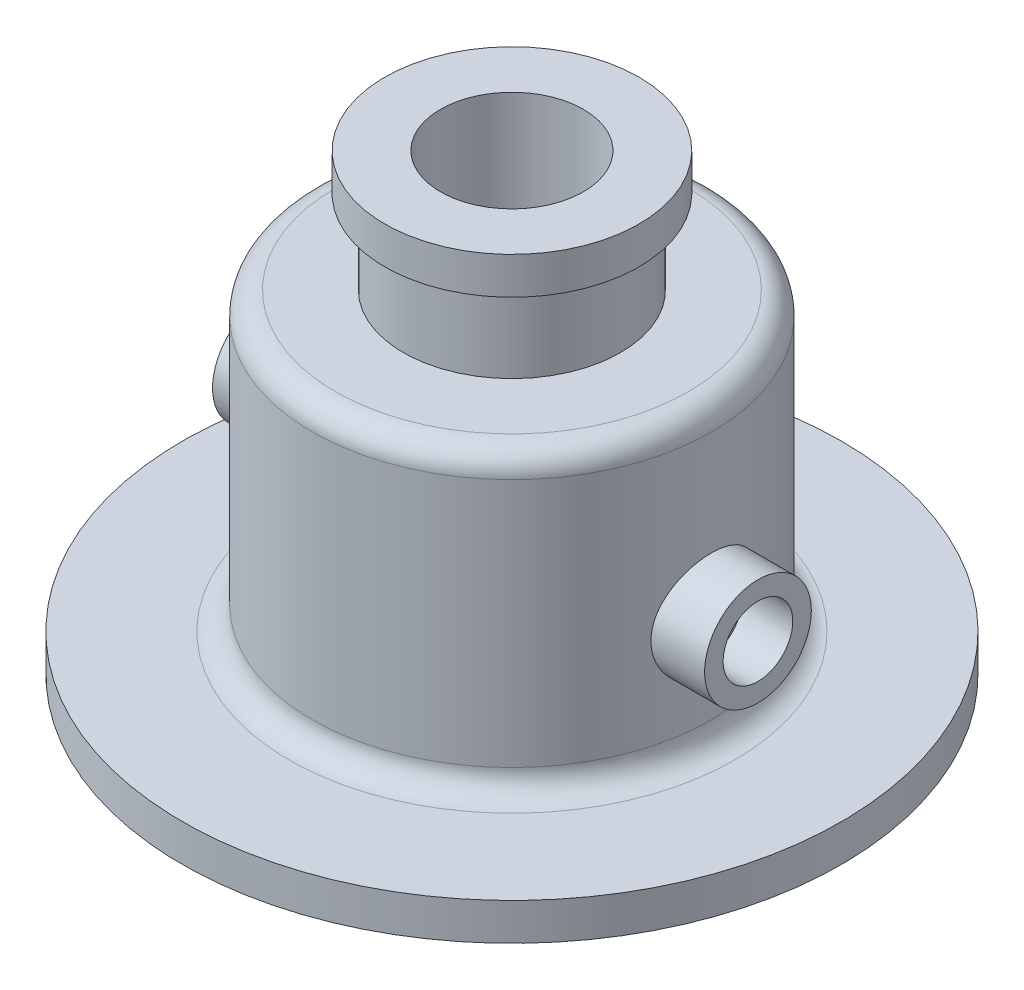
SolidWorks part; units mm, degrees
ref_plane "Front Plane" through (0, 0, 0) normal (0, 0, 1) x (1, 0, 0)
ref_plane "Top Plane" through (0, 0, 0) normal (0, 1, 0) x (1, 0, 0)
ref_plane "Right Plane" through (0, 0, 0) normal (1, 0, 0) x (0, 0, -1)
sketch "Sketch1" plane through (0, 0, 0) normal (0, 0, 1) x (1, 0, 0)
  line L0 (0, 0) -> (0, 43534.5217) construction
  line L1 (0, 0) -> (-43534.5217, 0) construction
  line L2 (15.4, 52.7) -> (15.4, 16.7)
  line L3 (15.4, 16.7) -> (23.4, 16.7)
  line L4 (23.4, 16.7) -> (23.4, 18.7)
  line L5 (23.4, 18.7) -> (30, 18.7)
  line L6 (35, 13.7) -> (35, -27)
  line L7 (30, -32) -> (25, -32)
  line L8 (25, -32) -> (25, -50)
  line L9 (25, -50) -> (32, -50)
  line L10 (32, -50) -> (32, -47)
  line L11 (34, -45) -> (71, -45)
  line L12 (71, -45) -> (71, -37)
  line L13 (71, -37) -> (48, -37)
  line L14 (43, -32) -> (43, 21.7)
  line L15 (38, 26.7) -> (23.4, 26.7)
  line L16 (23.4, 26.7) -> (23.4, 44.7)
  line L17 (23.4, 44.7) -> (27.4, 44.7)
  line L18 (27.4, 44.7) -> (27.4, 52.7)
  line L19 (27.4, 52.7) -> (15.4, 52.7)
  arc A0 (32, -47) -> (34, -45) centre (34, -47) cw
  arc A1 (48, -37) -> (43, -32) centre (48, -32) cw
  arc A2 (35, -27) -> (30, -32) centre (30, -27) cw
  arc A3 (30, 18.7) -> (35, 13.7) centre (30, 13.7) cw
  arc A4 (43, 21.7) -> (38, 26.7) centre (38, 21.7) ccw
  point P18 (23.4, 35.7)
  point P24 (28.5, -50)
  dimension "D19" = 2
  dimension "D20" = 5
  dimension "D1" = 7
  dimension "D2" = 8
  dimension "D3" = 2
  dimension "D4" = 8
  dimension "D5" = 8
  dimension "D6" = 8
  dimension "D7" = 48.7
  dimension "D8" = 15.4
  dimension "D9" = 8
  dimension "D10" = 35
  dimension "D11" = 5
  dimension "D12" = 25
  dimension "D13" = 71
  dimension "D14" = 34
  dimension "D15" = 4
  dimension "D16" = 18
  dimension "D17" = 5
  dimension "D18" = 50
revolve "Revolve1" add sketch "Sketch1" angle 360 about L0
chamfer "Chamfer1" distance 2 angle 45 1 edges at (0, 16.7, -15.4)
ref_plane "Plane1" through (53, 0, 0) normal (1, 0, 0) x (0, 0, -1)
ref_axis "Axis1" through (0, 52.7, 0) along (0, -1, 0)
sketch "Sketch2" plane through (53, 0, 0) normal (1, 0, 0) x (0, 0, -1)
  line L0 (-34, -45) -> (34, -45) construction
  circle A0 centre (0, -12.35) radius 7.5
  circle A1 centre (0, -12.35) radius 11.5
  dimension "D1" = 23
  dimension "D2" = 15
  dimension "D3" = 32.65
extrude "Boss-Extrude1" add sketch "Sketch2" against normal blind 106
sketch "Sketch3" plane through (0, 0, 0) normal (1, 0, 0) x (0, 0, -1)
  line L0 (0, 14.9003) -> (0, -27.9154) construction
  line L3 (0, 10.0895) -> (35, 10.0895)
  line L4 (35, 10.0895) -> (35, -27.9154)
  line L5 (35, -27.9154) -> (0, -27.9154)
  line L6 (43, -32) -> (43, 21.7) construction
  line L7 (0, -27.9154) -> (0, 10.0895)
  line L8 (0, 10.0895) -> (0, -27.9154)
  dimension "D1" = 8
revolve "Cut-Revolve1" cut sketch "Sketch3" angle 360 about L0 region at (0, -8.9129, -17.5)
